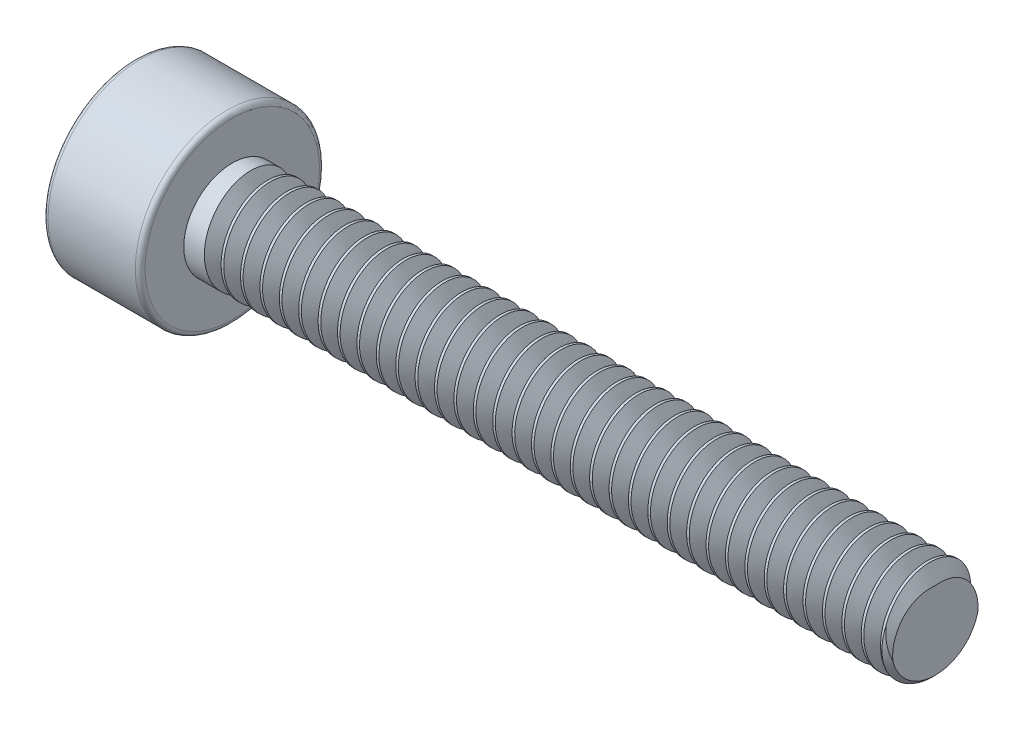
SolidWorks part; units mm, degrees
material "Cast Carbon Steel"
ref_plane "Front Plane" through (0, 0, 0) normal (0, 0, 1) x (1, 0, 0)
ref_plane "Top Plane" through (0, 0, 0) normal (0, 1, 0) x (1, 0, 0)
ref_plane "Right Plane" through (0, 0, 0) normal (1, 0, 0) x (0, 0, -1)
sketch "Sketch1" plane through (0, 0, 0) normal (0, 0, 1) x (1, 0, 0)
  line L0 (0, 0) -> (-85.5263, 0) construction
  line L1 (0, 0) -> (0, 1.8)
  line L2 (-0.1, 1.9) -> (-1.9, 1.9)
  line L3 (-2, 1.8) -> (-2, 0)
  line L4 (-2, 0) -> (0, 0)
  arc A0 (-1.9, 1.9) -> (-2, 1.8) centre (-1.9, 1.8) ccw
  arc A1 (0, 1.8) -> (-0.1, 1.9) centre (-0.1, 1.8) ccw
  dimension "head-round" = 0.1
  dimension "head-dia" = 3.8
  dimension "head-hight" = 2
revolve "Revolve1" add sketch "Sketch1" angle 360 about L0
sketch "Sketch2" plane through (-2, 0, 0) normal (-1, 0, 0) x (0, 0, 1)
  line L1 (0.866, 0) -> (0.433, 0.75)
  line L2 (0.433, 0.75) -> (-0.433, 0.75)
  line L3 (-0.433, 0.75) -> (-0.866, 0)
  line L4 (-0.866, 0) -> (-0.433, -0.75)
  line L5 (-0.433, -0.75) -> (0.433, -0.75)
  line L6 (0.433, -0.75) -> (0.866, 0)
  circle A0 centre (0, 0) radius 0.75 construction
  dimension "NV" = 1.5
extrude "Extrude1" cut sketch "Sketch2" against normal blind 1
sketch "Sketch3" plane through (0, 0, 0) normal (0, 0, 1) x (1, 0, 0)
  line L0 (0, 0) -> (4.4714, 0) construction
  line L1 (14.5, 0.9) -> (14.4, 1)
  line L2 (0, 0) -> (14.5, 0)
  line L3 (0, 0) -> (0, 1)
  line L4 (0, 1) -> (14.4, 1)
  line L5 (14.5, 0) -> (14.5, 0.9)
  point P3 (14.5, 1)
  dimension "45-cut" = 0.1
  dimension "D2" = 45
  dimension "lenght" = 14.5
  dimension "M" = 2
revolve "Revolve2" add sketch "Sketch3" angle 360 about L0
sketch "Sketch4" plane through (0, 0, 0) normal (0, 0, 1) x (1, 0, 0)
  line L0 (14.6691, 1.1) -> (14.9, 0.7)
  line L1 (14.9, 0.7) -> (15.1309, 1.1)
  line L2 (15.1309, 1.1) -> (14.6691, 1.1)
  line L3 (14.9, 0.4371) -> (14.9, 1.3714) construction
  line L4 (14.5, -0.9) -> (14.5, 0.9) construction
  line L5 (0, 0) -> (4.3833, 0) construction
  dimension "D1" = 60
  dimension "D2" = 30
  dimension "cut-pith1" = 0.4
  dimension "cut-dia" = 1.4
  dimension "pith1" = 0.4
sketch "Sketch5" plane through (14.5, 0, 0) normal (1, 0, 0) x (0, 0, -1)
  circle A0 centre (0, 0) radius 1
  dimension "helix-dim" = 2
curve "Helix/Spiral1" pitch 0.4 height 14.6 radius 1 centre (14.5, 0, 0) axis (-1, 0, 0) start towards (0, 1, 0) parameters "pith"=0.4
sweep "Cut-Sweep2" cut profiles "Sketch4" path "Helix/Spiral1" align with end faces yes
